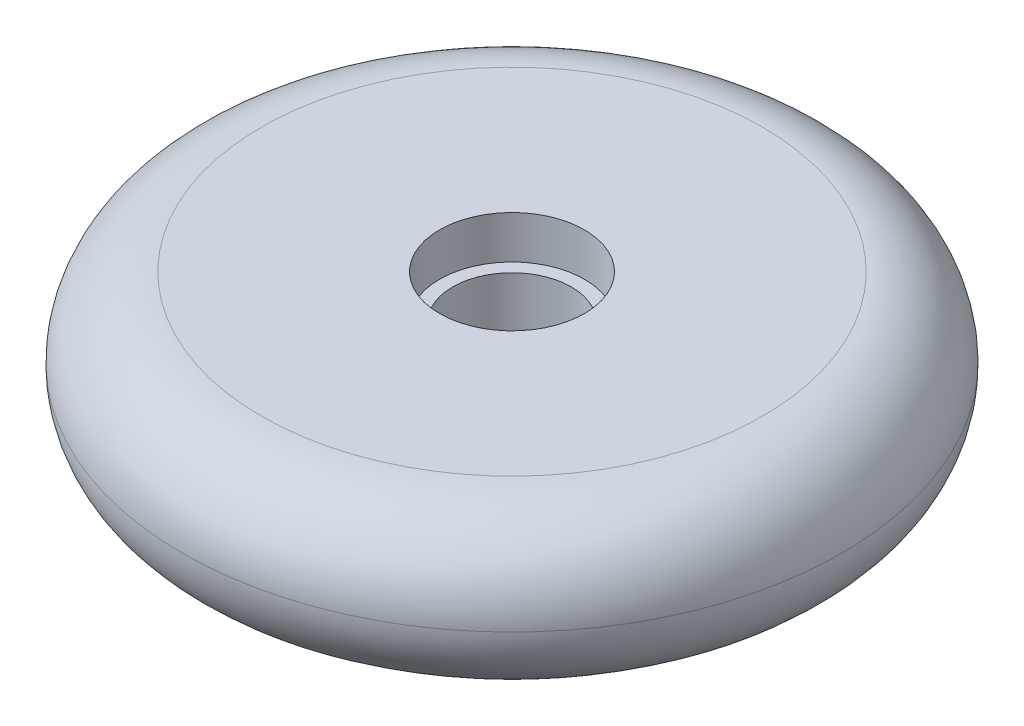
SolidWorks part; units mm, degrees
ref_plane "Front Plane" through (0, 0, 0) normal (0, 0, 1) x (1, 0, 0)
ref_plane "Top Plane" through (0, 0, 0) normal (0, 1, 0) x (1, 0, 0)
ref_plane "Right Plane" through (0, 0, 0) normal (1, 0, 0) x (0, 0, -1)
sketch "Sketch1" plane through (0, 0, 0) normal (0, 1, 0) x (1, 0, 0)
  circle A0 centre (0, 0) radius 50
  dimension "D1" = 100
extrude "Boss-Extrude1" add sketch "Sketch1" along normal blind 24
fillet "Fillet1" radius 12 2 edges at (0, 0, 50) (0, 24, 50)
sketch "Sketch2" plane through (0, 24, 0) normal (0, 1, 0) x (1, 0, 0)
  circle A0 centre (0, 0) radius 11
  dimension "D1" = 22
extrude "Cut-Extrude1" cut sketch "Sketch2" against normal blind 6.5
sketch "Sketch3" plane through (0, 0, 0) normal (0, -1, 0) x (1, 0, 0)
  circle A0 centre (0, 0) radius 11
  dimension "D1" = 22
extrude "Cut-Extrude2" cut sketch "Sketch3" against normal blind 6.5
sketch "Sketch4" plane through (0, 6.5, 0) normal (0, -1, 0) x (1, 0, 0)
  circle A0 centre (0, 0) radius 9
  dimension "D1" = 18
extrude "Cut-Extrude3" cut sketch "Sketch4" against normal through all
